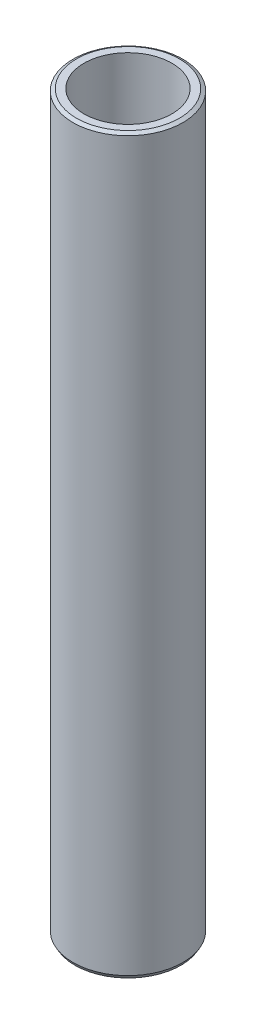
SolidWorks part; units mm, degrees
ref_plane "Front Plane" through (0, 0, 0) normal (0, 0, 1) x (1, 0, 0)
ref_plane "Top Plane" through (0, 0, 0) normal (0, 1, 0) x (1, 0, 0)
ref_plane "Right Plane" through (0, 0, 0) normal (1, 0, 0) x (0, 0, -1)
sketch "Sketch1" plane through (0, 0, 0) normal (0, 1, 0) x (1, 0, 0)
  circle A0 centre (0, 0) radius 45
  dimension "SHAFT_OD" = 90
extrude "Boss-Extrude1" add sketch "Sketch1" along normal blind 600
sketch "Sketch2" plane through (0, 0, 0) normal (0, 1, 0) x (1, 0, 0)
  circle A0 centre (0, 0) radius 35.9891
  dimension "BORE_D" = 71.9782
extrude "Cut-Extrude1" cut sketch "Sketch2" along normal through all
chamfer "Chamfer1" distance 1.6535 angle 60 2 edges at (0, 600, 45) (0, 0, 45) first distance on face at (0, 600, 45) first distance on face at (0, 0, 35.9891)
